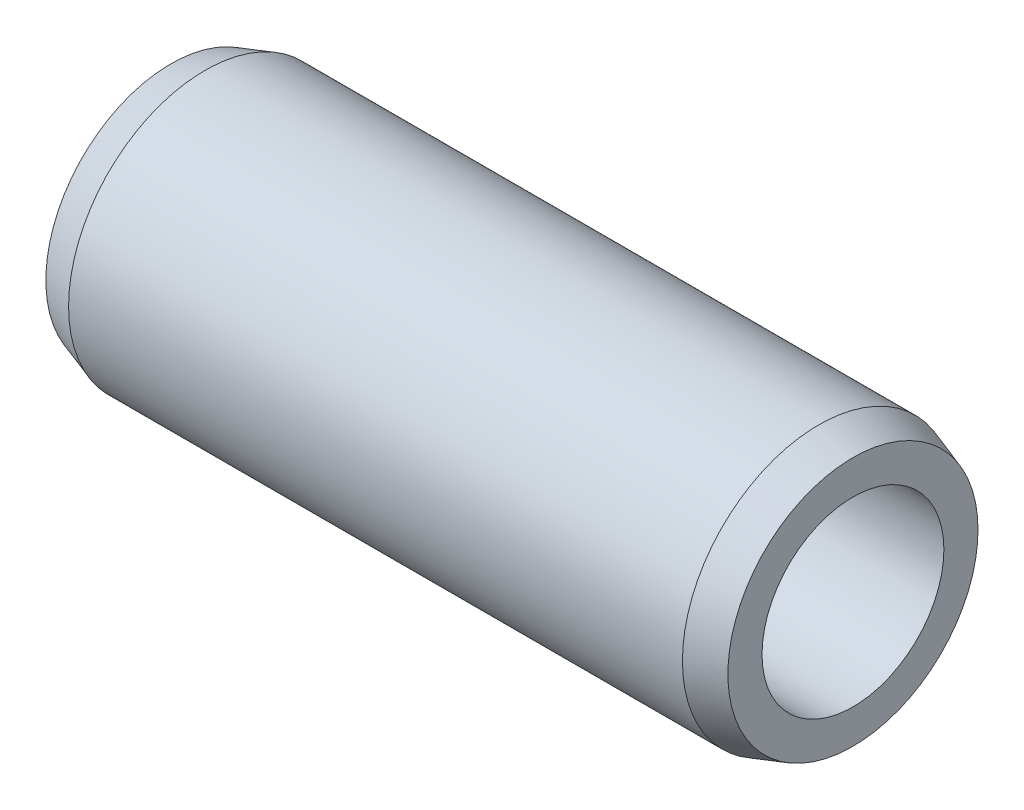
SolidWorks part; units mm, degrees
ref_plane "Front Plane" through (0, 0, 0) normal (0, 0, 1) x (1, 0, 0)
ref_plane "Top Plane" through (0, 0, 0) normal (0, 1, 0) x (1, 0, 0)
ref_plane "Right Plane" through (0, 0, 0) normal (1, 0, 0) x (0, 0, -1)
sketch "Sketch1" plane through (0, 0, 0) normal (1, 0, 0) x (0, 0, -1)
  circle A0 centre (0, 0) radius 6
  circle A1 centre (0, 0) radius 4
  dimension "D1" = 8
  dimension "D2" = 12
extrude "Boss-Extrude1" add sketch "Sketch1" along normal blind 30
chamfer "Chamfer2" distance 0.5 distance2 1.5 2 edges at (30, 0, -6) (0, 0, -6) first distance on face at (30, 0, -6) first distance on face at (0, 0, -6)
equation "\"d_inner\"= 8"
equation "\"d_outer\"= 12"
equation "\"l\"= 30"
equation "\"D1@Sketch1\"=\"d_inner\""
equation "\"D2@Sketch1\"=\"d_outer\""
equation "\"D1@Boss-Extrude1\"=\"l\""
